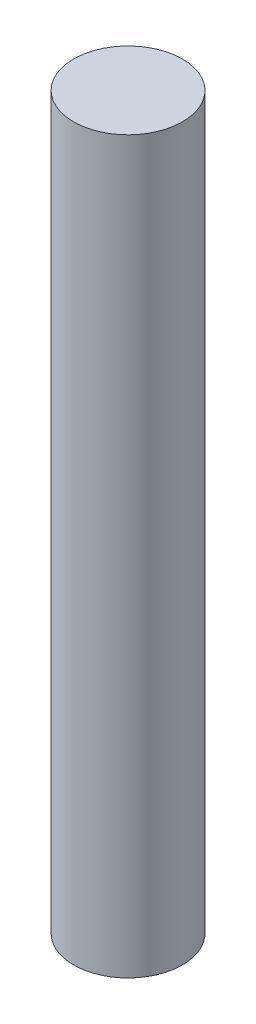
SolidWorks part; units mm, degrees
ref_plane "Front Plane" through (0, 0, 0) normal (0, 0, 1) x (1, 0, 0)
ref_plane "Top Plane" through (0, 0, 0) normal (0, 1, 0) x (1, 0, 0)
ref_plane "Right Plane" through (0, 0, 0) normal (1, 0, 0) x (0, 0, -1)
sketch "Sketch1" plane through (0, 0, 0) normal (0, 1, 0) x (1, 0, 0)
  circle A0 centre (0, 0) radius 3.175
  dimension "D1" = 6.35
sketch "Sketch2" plane through (0, 0, 0) normal (1, 0, 0) x (0, 0, -1)
  line L0 (0, 0) -> (0, 42.5953)
  circle A0 centre (0, 0) radius 42.5953 construction
extrude "Boss-Extrude1" add sketch "Sketch1" along normal up to vertex (42.5953 mm away) contours A0 up to point (0, 42.5953, 0)
